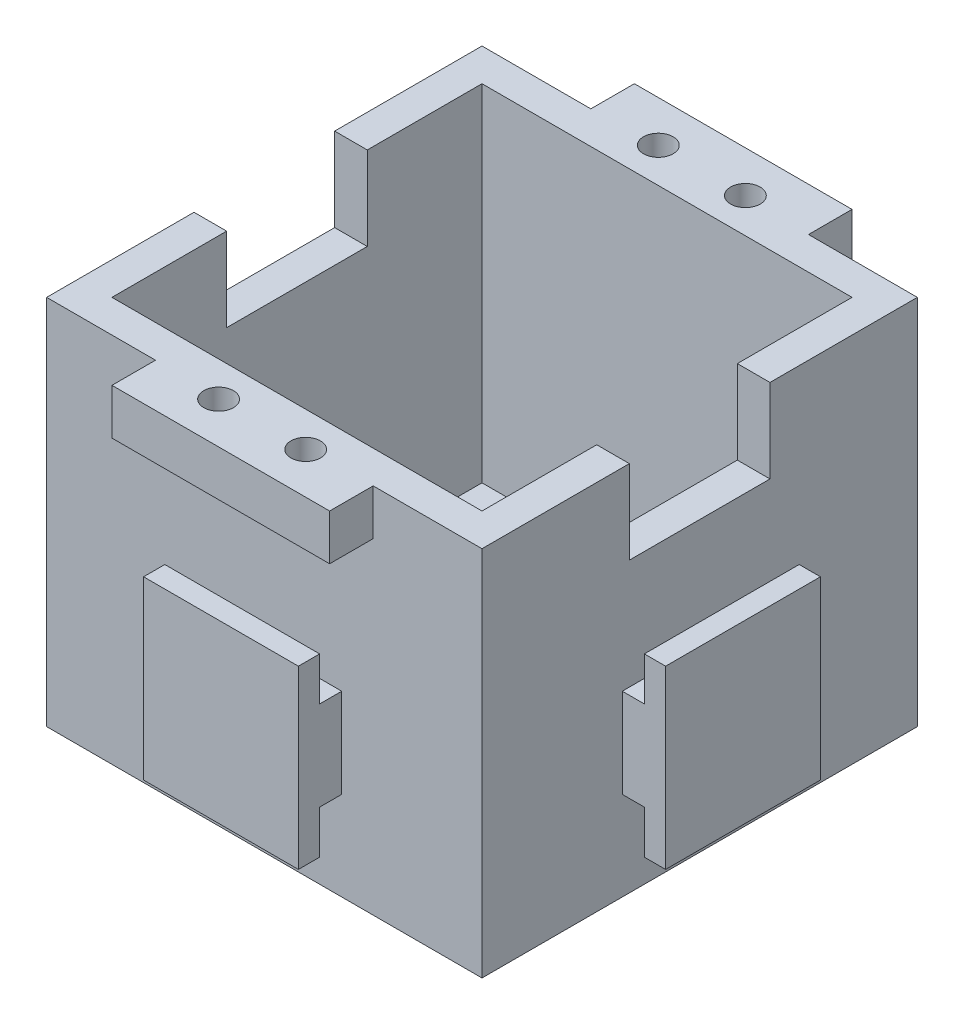
SolidWorks part; units mm, degrees
material "ABS"
ref_plane "Front Plane" through (0, 0, 0) normal (0, 0, 1) x (1, 0, 0)
ref_plane "Top Plane" through (0, 0, 0) normal (0, 1, 0) x (1, 0, 0)
ref_plane "Right Plane" through (0, 0, 0) normal (1, 0, 0) x (0, 0, -1)
sketch "Sketch1" plane through (0, 0, 0) normal (0, 1, 0) x (1, 0, 0)
  line L1 (-21.25, 21.25) -> (21.25, 21.25)
  line L2 (-21.25, 21.25) -> (-21.25, -21.25)
  line L3 (-21.25, -21.25) -> (21.25, -21.25)
  line L4 (21.25, 21.25) -> (21.25, -21.25)
  line L5 (-21.25, 21.25) -> (21.25, -21.25) construction
  line L6 (-21.25, -21.25) -> (21.25, 21.25) construction
  line L7 (-25, 25) -> (25, 25)
  line L8 (-25, 25) -> (-25, -25)
  line L9 (-25, -25) -> (25, -25)
  line L10 (25, 25) -> (25, -25)
  line L11 (-25, 25) -> (25, -25) construction
  line L12 (-25, -25) -> (25, 25) construction
  point P0 (0, 0)
  point P6 (0, 0)
  dimension "D1" = 42.5
  dimension "D2" = 42.5
  dimension "D3" = 50
  dimension "D4" = 50
extrude "Boss-Extrude1" add sketch "Sketch1" along normal blind 3 contours L8 L9 L10 L7
sketch "Sketch3" plane through (0, 3, 0) normal (0, 1, 0) x (1, 0, 0)
  line L1 (-25, 25) -> (25, 25)
  line L2 (-25, 25) -> (-25, -25)
  line L3 (-25, -25) -> (25, -25)
  line L4 (25, 25) -> (25, -25)
  line L5 (-25, 25) -> (25, -25) construction
  line L6 (-25, -25) -> (25, 25) construction
  line L7 (-21.25, 21.25) -> (21.25, 21.25)
  line L8 (-21.25, 21.25) -> (-21.25, -21.25)
  line L9 (-21.25, -21.25) -> (21.25, -21.25)
  line L10 (21.25, 21.25) -> (21.25, -21.25)
  line L11 (-21.25, 21.25) -> (21.25, -21.25) construction
  line L12 (-21.25, -21.25) -> (21.25, 21.25) construction
  point P0 (0, 0)
  point P7 (0, 0)
  dimension "D1" = 42.5
extrude "Boss-Extrude2" add sketch "Sketch3" along normal blind 39.7
sketch "Sketch19" plane through (25, 0, 0) normal (1, 0, 0) x (0, 0, -1)
  line L0 (25, 0) -> (-25, 0) construction
  line L5 (-25, 42.7) -> (25, 42.7) construction
  line L11 (-8.075, 42.7) -> (8.075, 42.7)
  line L12 (-8.075, 42.7) -> (-8.075, 33.1)
  line L17 (-8.075, 33.1) -> (8.075, 33.1)
  line L18 (8.075, 42.7) -> (8.075, 33.1)
  point P8 (0, 0)
  point P9 (0, 42.7)
  line M27 (25, 42.7) -> (-25, 42.7)
  dimension "D1" = 16.15
  dimension "D2" = 9.6
extrude "Cut-Extrude5" cut sketch "Sketch19" against normal blind 5 and the other way through all contours L18 L12 L17 M27 region at (25, 37.9, 0)
sketch "Sketch33" plane through (0, 0, 25) normal (0, 0, 1) x (1, 0, 0)
  line L0 (-25, 42.7) -> (25, 42.7) construction
  line L1 (-12.5, 42.7) -> (12.5, 42.7)
  line L2 (-12.5, 42.7) -> (-12.5, 37.45)
  line L3 (-12.5, 37.45) -> (12.5, 37.45)
  line L4 (12.5, 42.7) -> (12.5, 37.45)
  point P6 (0, 42.7)
  point P7 (0, 42.7)
  dimension "D1" = 5.25
  dimension "D2" = 25
extrude "Boss-Extrude14" add sketch "Sketch33" along normal blind 5
mirror "Mirror7" about plane through (0, 0, 0) normal (0, 0, 1) of "Boss-Extrude14"
sketch "Sketch21" plane through (0, 42.7, 0) normal (0, 1, 0) x (1, 0, 0)
  line L3 (-12.5, -30) -> (-12.5, -25) construction
  line L4 (12.5, -30) -> (12.5, -25) construction
  line L6 (12.5, -30) -> (-12.5, -30) construction
  line L7 (12.5, 30) -> (-12.5, 30) construction
  circle A0 centre (5, -25.25) radius 1.7
  circle A1 centre (-5, 25.25) radius 1.7
  circle A2 centre (5, 25.25) radius 1.7
  circle A3 centre (-5, -25.25) radius 1.7
  dimension "D1" = 3.4
  dimension "D4" = 3.4
  dimension "D7" = 3.4
  dimension "D8" = 3.4
  dimension "D9" = 4.75
  dimension "D5" = 7.5
  dimension "D3" = 7.5
  dimension "D2" = 4.75
  dimension "D6" = 4.75
  dimension "D10" = 4.75
  dimension "D11" = 0
  dimension "D12" = 0
extrude "Cut-Extrude6" cut sketch "Sketch21" against normal blind 5 contours A1 | A2 | A3 | A0
sketch "Sketch23" plane through (-25, 0, 0) normal (-1, 0, 0) x (0, 0, 1)
  line L0 (-25, 0) -> (25, 0) construction
  line L1 (-19.05, 0) -> (19.05, 0)
  line L2 (-19.05, 0) -> (-19.05, 42.7)
  line L3 (-19.05, 42.7) -> (19.05, 42.7)
  line L4 (19.05, 0) -> (19.05, 42.7)
  line L5 (-25, 42.7) -> (25, 42.7) construction
  line L6 (-19.05, 33.09) -> (19.05, 33.09)
  line L7 (-19.05, 42.7) -> (-11.43, 42.7)
  line L8 (-19.05, 42.7) -> (-19.05, 0)
  line L9 (-19.05, 0) -> (-11.43, 0)
  line L10 (-11.43, 42.7) -> (-11.43, 0)
  line L11 (19.05, 42.7) -> (11.43, 42.7)
  line L12 (19.05, 42.7) -> (19.05, 0)
  line L13 (19.05, 0) -> (11.43, 0)
  line L14 (11.43, 42.7) -> (11.43, 0)
  point P8 (0, 42.7)
  point P9 (0, 42.7)
  dimension "D1" = 38.1
  dimension "D2" = 7.62
  dimension "D3" = 7.62
  dimension "D4" = 9.61
sketch "Sketch27" plane through (0, 0, 0) normal (0, -1, 0) x (1, 0, 0)
  circle A0 centre (0, 0) radius 11.5
  point P3 (-15.5, 15.55)
  point P4 (15.5, 15.5)
  point P5 (15.5, -15.5)
  point P6 (-15.5, -15.5)
  dimension "D1" = 23
  dimension "D2" = 15.5
  dimension "D3" = 15.55
  dimension "D4" = 15.5
  dimension "D5" = 15.5
  dimension "D6" = 15.5
  dimension "D7" = 15.5
  dimension "D8" = 15.5
  dimension "D9" = 15.5
extrude "Cut-Extrude8" cut sketch "Sketch27" against normal up to next contours A0
sketch "Sketch29" plane through (0, 0, 0) normal (0, -1, 0) x (1, 0, 0)
  point P0 (-15.5, 15.5)
  point P1 (15.5, 15.5)
  point P2 (15.5, -15.5)
  point P3 (-15.5, -15.5)
  dimension "D1" = 15.5
  dimension "D2" = 15.5
  dimension "D3" = 15.5
  dimension "D4" = 15.5
hole_wizard "CSK for M3 Countersunk Flat Head Screw1" positions "3DSketch2" profile "Sketch30" countersink size "M3" standard "ISO" end condition up to next
sketch3d "3DSketch2"
  point P0 (-15.5, 0, 15.5)
  point P3 (15.5, 0, 15.5)
  point P6 (15.5, 0, -15.5)
  point P9 (-15.5, 0, -15.5)
sketch "Sketch30" plane through (-15.5, 0, 15.5) normal (1, 0, 0) x (0, 0, -1)
  line L0 (0, 0) -> (0, 3)
  line L1 (0, 3) -> (1.7, 3)
  line L2 (1.7, 3) -> (1.7, 1.45)
  line L3 (1.7, 1.45) -> (3.15, 0)
  line L5 (3.15, 0) -> (0, 0)
  line L6 (-1.7, 1.45) -> (-3.15, 0) construction
  line L11 (0, -6.35) -> (0, 107.95) construction
  dimension "Thru Hole Dia." = 3.4
  dimension "Thru Hole Depth" = 3
  dimension "Near C'Sink Dia." = 6.3
  dimension "Near C'Sink Angle" = 90
mirror "Mirror4" about plane through (0, 0, 0) normal (1, 0, 0) of "Cut-Extrude5"
ref_plane "Plane1" through (0, 0, 0) normal (0, 0, 1) x (1, 0, 0)
sketch "Sketch34" plane through (0, 0, 25) normal (0, 0, 1) x (1, 0, 0)
  line L0 (8.89, 20.4724) -> (-8.89, 20.4724)
  line L1 (-8.89, 0) -> (8.89, 0)
  line L2 (-8.89, 0) -> (-8.89, 30.734)
  line L3 (-8.89, 30.734) -> (8.89, 30.734)
  line L4 (8.89, 0) -> (8.89, 30.734)
  line L5 (-8.89, 10.2108) -> (8.89, 10.2108)
  line L7 (-25, 0) -> (25, 0) construction
  point P14 (0, 0)
  point P15 (0, 0)
  dimension "D1" = 10.2108
  dimension "D2" = 10.2616
  dimension "D3" = 30.734
  dimension "D4" = 17.78
extrude "Boss-Extrude15" add sketch "Sketch34" along normal blind 4.9784 contours L2 L5 L4 L0 region at (0, 15.3416, 25)
sketch "Sketch35" plane through (0, 20.4724, 0) normal (0, 1, 0) x (1, 0, 0)
  line L0 (8.89, -29.9784) -> (8.89, -25) construction
  line L1 (-8.89, -29.9784) -> (8.89, -29.9784)
  line L2 (-8.89, -29.9784) -> (-8.89, -27.54)
  line L3 (-8.89, -27.54) -> (8.89, -27.54)
  line L4 (8.89, -29.9784) -> (8.89, -27.54)
  dimension "D1" = 2.4384
extrude "Boss-Extrude16" add sketch "Sketch35" along normal blind 4.9784
ref_plane "Plane5" through (0, 15.3416, 0) normal (0, 1, 0) x (1, 0, 0)
mirror "Mirror8" about plane through (0, 15.3416, 0) normal (0, 1, 0) of "Boss-Extrude16"
ref_axis "Axis1" through (0, 44.835, 0) along (0, -1, 0)
pattern_circular "CirPattern1" count 4 over 360 about axis through (0, 44.835, 0) along (0, -1, 0) of "Boss-Extrude15", "Boss-Extrude16", "Mirror8"
